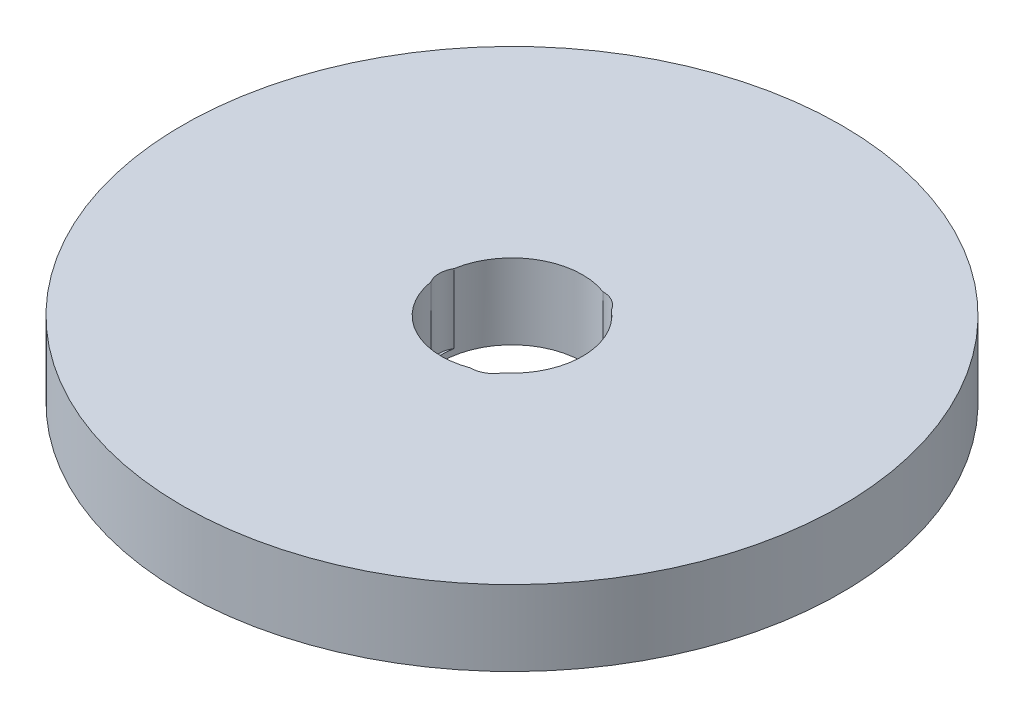
SolidWorks part; units mm, degrees
ref_plane "Front Plane" through (0, 0, 0) normal (0, 0, 1) x (1, 0, 0)
ref_plane "Top Plane" through (0, 0, 0) normal (0, 1, 0) x (1, 0, 0)
ref_plane "Right Plane" through (0, 0, 0) normal (1, 0, 0) x (0, 0, -1)
sketch "Sketch1" plane through (0, 0, 0) normal (0, 1, 0) x (1, 0, 0)
  circle A0 centre (0, 0) radius 70
  dimension "FLANGE_OD" = 140
extrude "Boss-Extrude1" add sketch "Sketch1" along normal blind 16
sketch "Sketch2" plane through (0, 0, 0) normal (0, 1, 0) x (1, 0, 0)
  circle A0 centre (0, 0) radius 15
  dimension "BORE_D" = 30
extrude "Cut-Extrude1" cut sketch "Sketch2" along normal through all
sketch "Sketch3" plane through (0, 16, 0) normal (0, 1, 0) x (1, 0, 0)
  circle A0 centre (0, 0) radius 10.6783 construction
  circle A1 centre (-10.6783, 0) radius 4.7905
  dimension "BOLT_D" = 9.581
  dimension "BOLT_PCD" = 21.3566
extrude "Cut-Extrude2" cut sketch "Sketch3" against normal blind 14.7093
pattern_circular "CirPattern1" count 3 over 360 about axis through (0, 0, 0) along (0, 1, 0) of "Cut-Extrude2"
